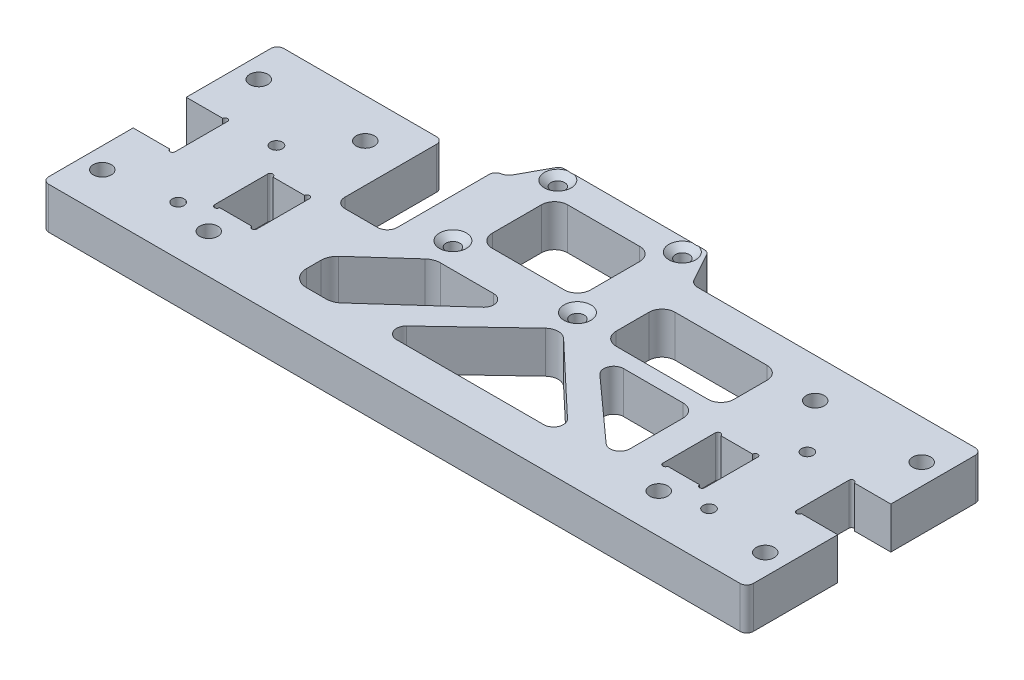
SolidWorks part; units mm, degrees
material "6061 Alloy"
ref_plane "Front Plane" through (0, 0, 0) normal (0, 0, 1) x (1, 0, 0)
ref_plane "Top Plane" through (0, 0, 0) normal (0, 1, 0) x (1, 0, 0)
ref_plane "Right Plane" through (0, 0, 0) normal (1, 0, 0) x (0, 0, -1)
sketch "Sketch1" plane through (0, 0, 0) normal (0, 1, 0) x (1, 0, 0)
  line L0 (107.5, 76.65) -> (107.5, 0) construction
  line L6 (32.7004, 36.1) -> (32.7004, 19.9)
  line L8 (45.6, 36) -> (45.6, 20)
  line L13 (0, 71.75) -> (69.5, 71.75)
  line L14 (69.5, 71.75) -> (75.5, 82.75)
  line L15 (75.5, 82.75) -> (120.5, 82.75)
  line L16 (120.5, 82.75) -> (126.5, 71.75)
  line L17 (126.5, 71.75) -> (215, 71.75)
  line L18 (32.7004, 28) -> (45.6, 28) construction
  line L19 (34.3004, 36.1) -> (44.0063, 36.1)
  line L20 (34.3004, 19.9) -> (44.0063, 19.9)
  line L21 (182.2996, 36.1) -> (182.2996, 19.9)
  line L22 (180.6996, 36.1) -> (170.9937, 36.1)
  line L23 (169.4, 36) -> (169.4, 20)
  line L24 (180.6996, 19.9) -> (170.9937, 19.9)
  line L25 (12.7, 35.875) -> (0, 35.875) construction
  line L29 (12.7, 43.975) -> (12.7, 27.775)
  line L30 (11.1189, 43.975) -> (0, 43.975)
  line L31 (11.1189, 27.775) -> (0, 27.775)
  line L32 (0, 27.775) -> (0, 0)
  line L33 (0, 43.975) -> (0, 71.75)
  line L34 (202.3, 35.875) -> (215, 35.875) construction
  line L35 (215, 43.975) -> (215, 71.75)
  line L36 (215, 27.775) -> (215, 0)
  line L37 (203.8811, 27.775) -> (215, 27.775)
  line L38 (203.8811, 43.975) -> (215, 43.975)
  line L39 (202.3, 43.975) -> (202.3, 27.775)
  line L44 (107.5, 0) -> (215, 0)
  line L46 (107.5, 0) -> (0, 0)
  circle A0 centre (38.85, 59.75) radius 2.75
  circle A5 centre (38.85, 12) radius 2.75
  circle A6 centre (176.15, 59.75) radius 2.75
  circle A7 centre (176.15, 12) radius 2.75
  arc A8 (32.7004, 36.1) -> (34.3004, 36.1) centre (33.5004, 36.1) cw
  arc A9 (45.6, 36) -> (44.0063, 36.1) centre (44.8, 36) ccw
  arc A10 (32.7004, 19.9) -> (34.3004, 19.9) centre (33.5004, 19.9) ccw
  arc A11 (45.6, 20) -> (44.0063, 19.9) centre (44.8, 20) cw
  arc A12 (182.2996, 19.9) -> (180.6996, 19.9) centre (181.4996, 19.9) cw
  arc A13 (182.2996, 36.1) -> (180.6996, 36.1) centre (181.4996, 36.1) ccw
  arc A14 (169.4, 36) -> (170.9937, 36.1) centre (170.2, 36) cw
  arc A15 (169.4, 20) -> (170.9937, 19.9) centre (170.2, 20) ccw
  circle A16 centre (6.35, 12) radius 2.75
  circle A17 centre (6.35, 59.75) radius 2.75
  arc A18 (12.7, 27.775) -> (11.1189, 27.775) centre (11.9095, 27.8976) cw
  arc A19 (12.7, 43.975) -> (11.1189, 43.975) centre (11.9095, 43.8524) ccw
  arc A20 (202.3, 43.975) -> (203.8811, 43.975) centre (203.0905, 43.8524) cw
  arc A21 (202.3, 27.775) -> (203.8811, 27.775) centre (203.0905, 27.8976) ccw
  circle A22 centre (208.65, 59.75) radius 2.75
  circle A23 centre (208.65, 12) radius 2.75
  dimension "D12" = 5.5
  dimension "D16" = 5.5
  dimension "D17" = 0.8
  dimension "D18" = 0.8
  dimension "D19" = 0.8
  dimension "D20" = 0.8
  dimension "D21" = 5.5
  dimension "D22" = 5.5
  dimension "D27" = 0.8
  dimension "D1" = 215
  dimension "D2" = 71.75
  dimension "D5" = 61.9
  dimension "D6" = 12.9
  dimension "D4" = 11
  dimension "D7" = 6
  dimension "D8" = 38
  dimension "D10" = 45
  dimension "D11" = 16.2
  dimension "D14" = 6
  dimension "D13" = 12
  dimension "D25" = 16.2
  dimension "D3" = 12
  dimension "D23" = 16.2
  dimension "D26" = 12.7
extrude "Boss-Extrude1" add sketch "Sketch1" along normal blind 12.7
sketch "Sketch2" plane through (0, 12.7, 0) normal (0, 1, 0) x (1, 0, 0)
  line L1 (50.6, 85.2461) -> (66.6, 85.2461)
  line L2 (50.6, 85.2461) -> (50.6, 38.75)
  line L3 (50.6, 38.75) -> (66.6, 38.75)
  line L4 (66.6, 85.2461) -> (66.6, 38.75)
  line L5 (45.6, 20) -> (45.6, 36) construction
  line L12 (69.5, 71.75) -> (0, 71.75) construction
  dimension "D1" = 5
  dimension "D2" = 16
  dimension "D3" = 33
extrude "Cut-Extrude1" cut sketch "Sketch2" against normal through all
sketch "Sketch3" plane through (0, 12.7, 0) normal (0, 1, 0) x (1, 0, 0)
  line L1 (66.6, 38.75) -> (66.6, 71.75) construction
  line L2 (120.5, 82.75) -> (75.5, 82.75) construction
  circle A0 centre (78.6, 78.75) radius 2.1
  circle A1 centre (78.6, 46.75) radius 2.1
  circle A2 centre (116.6, 78.75) radius 2.1
  circle A3 centre (116.6, 46.75) radius 2.1
  dimension "D2" = 4.2
  dimension "D5" = 4.2
  dimension "D8" = 32
  dimension "D1" = 4
  dimension "D3" = 12
  dimension "D4" = 32
  dimension "D7" = 38
  dimension "D6" = 2
extrude "Cut-Extrude2" cut sketch "Sketch3" against normal through all
sketch "Sketch5" plane through (0, 12.7, 0) normal (0, 1, 0) x (1, 0, 0)
  line L3 (98.7821, 39) -> (82.5187, 39)
  line L11 (78.0261, 13.2835) -> (100.789, 33.7701)
  line L12 (66.6, 38.75) -> (66.6, 71.75) construction
  line L13 (115.8513, 37.7761) -> (94.0759, 17.1795)
  line L14 (118.6, 40.376) -> (118.6, 12) construction
  line L15 (96.1374, 12) -> (141.0626, 12)
  line L16 (121.3487, 37.7761) -> (143.1241, 17.1795)
  line L17 (138.4179, 39) -> (156.6, 39)
  line L18 (155.5931, 16.5062) -> (136.411, 33.7701)
  line L19 (160.6, 35) -> (160.6, 18.7361)
  line L20 (120.5, 82.75) -> (75.5, 82.75) construction
  line L21 (86.6, 73.75) -> (108.6, 73.75)
  line L22 (82.6, 69.75) -> (82.6, 54.75)
  line L23 (86.6, 50.75) -> (108.6, 50.75)
  line L24 (112.6, 69.75) -> (112.6, 54.75)
  line L25 (215, 71.75) -> (126.5, 71.75) construction
  line L26 (131.4, 61.75) -> (159.4, 61.75)
  line L27 (127.4, 57.75) -> (127.4, 47.75)
  line L28 (131.4, 43.75) -> (159.4, 43.75)
  line L29 (163.4, 57.75) -> (163.4, 47.75)
  line L30 (79.1739, 37.7165) -> (65.279, 25.2111)
  line L31 (169.4, 36) -> (169.4, 20) construction
  line L32 (63.6239, 21.4947) -> (63.6239, 17)
  line L33 (68.6239, 12) -> (74.6813, 12)
  arc A0 (121.3487, 37.7761) -> (115.8513, 37.7761) centre (118.6, 34.8701) ccw
  arc A1 (160.6, 35) -> (156.6, 39) centre (156.6, 35) ccw
  arc A3 (112.6, 69.75) -> (108.6, 73.75) centre (108.6, 69.75) ccw
  arc A4 (108.6, 50.75) -> (112.6, 54.75) centre (108.6, 54.75) ccw
  arc A5 (82.6, 54.75) -> (86.6, 50.75) centre (86.6, 54.75) ccw
  arc A6 (82.6, 69.75) -> (86.6, 73.75) centre (86.6, 69.75) cw
  arc A7 (155.5931, 16.5062) -> (160.6, 18.7361) centre (157.6, 18.7361) ccw
  arc A8 (136.411, 33.7701) -> (138.4179, 39) centre (138.4179, 36) cw
  arc A10 (141.0626, 12) -> (143.1241, 17.1795) centre (141.0626, 15) ccw
  arc A11 (96.1374, 12) -> (94.0759, 17.1795) centre (96.1374, 15) cw
  arc A12 (100.789, 33.7701) -> (98.7821, 39) centre (98.7821, 36) ccw
  arc A13 (163.4, 57.75) -> (159.4, 61.75) centre (159.4, 57.75) ccw
  arc A14 (159.4, 43.75) -> (163.4, 47.75) centre (159.4, 47.75) ccw
  arc A15 (127.4, 47.75) -> (131.4, 43.75) centre (131.4, 47.75) ccw
  arc A16 (127.4, 57.75) -> (131.4, 61.75) centre (131.4, 57.75) cw
  arc A17 (79.1739, 37.7165) -> (82.5187, 39) centre (82.5187, 34) cw
  arc A18 (63.6239, 21.4947) -> (65.279, 25.2111) centre (68.6239, 21.4947) cw
  arc A19 (68.6239, 12) -> (63.6239, 17) centre (68.6239, 17) cw
  arc A20 (74.6813, 12) -> (78.0261, 13.2835) centre (74.6813, 17) ccw
  point P25 (160.6, 39)
  point P33 (112.6, 50.75)
  point P36 (82.6, 50.75)
  point P39 (82.6, 73.75)
  point P42 (160.6, 12)
  point P45 (130.6, 39)
  point P48 (76.6, 12)
  point P51 (148.6, 12)
  point P54 (88.6, 12)
  point P57 (106.6, 39)
  point P68 (163.4, 61.75)
  point P71 (163.4, 43.75)
  point P76 (127.4, 61.75)
  dimension "D11" = 4
  dimension "D12" = 3
  dimension "D13" = 3
  dimension "D14" = 3
  dimension "D19" = 4
  dimension "D2" = 5
  dimension "D4" = 5
  dimension "D3" = 12
  dimension "D6" = 30
  dimension "D7" = 9
  dimension "D8" = 16
  dimension "D9" = 23
  dimension "D10" = 30
  dimension "D15" = 10
  dimension "D16" = 18
  dimension "D17" = 6
  dimension "D18" = 36
extrude "Cut-Extrude3" cut sketch "Sketch5" against normal through all
fillet "Fillet1" radius 3 4 edges at (69.5, 6.35, -71.75) (66.6, 6.35, -38.75) (50.6, 6.35, -38.75) (126.5, 6.35, -71.75)
fillet "Fillet2" radius 2 8 edges at (215, 6.35, -71.75) (120.5, 6.35, -82.75) (75.5, 6.35, -82.75) (50.6, 6.35, -71.75) (66.6, 6.35, -71.75) (0, 6.35, -71.75) (215, 6.35, 0) (0, 6.35, 0)
sketch "Sketch6" plane through (0, 12.7, 0) normal (0, 1, 0) x (1, 0, 0)
  line L0 (2, 0) -> (213, 0) construction
  line L1 (107.5, 92.584) -> (107.5, -38.973) construction
  line L2 (215, 2) -> (215, 27.775) construction
  circle A0 centre (188.5, 45) radius 1.8
  circle A1 centre (176.15, 59.75) radius 2.75 construction
  circle A2 centre (188.5, 15) radius 1.8
  circle A3 centre (26.5, 45) radius 1.8
  circle A4 centre (26.5, 15) radius 1.8
  dimension "D2" = 3.6
  dimension "D5" = 3.6
  dimension "D1" = 12.35
  dimension "D3" = 45
  dimension "D4" = 15
  dimension "D6" = 107.5
extrude "Cut-Extrude4" cut sketch "Sketch6" against normal through all
chamfer "Chamfer1" distance 2 angle 40 4 edges at (116.6, 12.7, -76.65) (116.6, 12.7, -44.65) (78.6, 12.7, -44.65) (78.6, 12.7, -76.65) first distance on face at (188.5, 12.7, -13.2)
equation "\"DriveMotorLength\"= 90mm"
equation "\"DriveMotorGap\"= 10mm"
equation "\"AluminumThickness\"= 0.5in"
equation "\"ChassisWidth\"= ( \"DriveMotorLength\" + \"AluminumThickness\" ) * 2 + \"DriveMotorGap\""
equation "\"RepeatMagnumHoleWidth\"= 19.05mm"
equation "\"MortiseWidth\"= 16mm"
equation "\"ChassisScrewThruHole\"= 5.5mm"
equation "\"D11@Sketch1\"=\"MortiseSlotWidth\""
equation "\"D12@Sketch1\"=\"ChassisScrewThruHole\""
equation "\"D16@Sketch1\"=\"ChassisScrewThruHole\""
equation "\"MortiseSlotWidth\"= 16.2mm"
equation "\"Dogbone\"= 0.8mm"
equation "\"D17@Sketch1\"=\"Dogbone\""
equation "\"D18@Sketch1\"=\"Dogbone\""
equation "\"D19@Sketch1\"=\"Dogbone\""
equation "\"D20@Sketch1\"=\"Dogbone\""
equation "\"D21@Sketch1\"=\"ChassisScrewThruHole\""
equation "\"D22@Sketch1\"=\"ChassisScrewThruHole\""
equation "\"D27@Sketch1\"=\"Dogbone\""
equation "\"D23@Sketch1\"=\"MortiseSlotWidth\""
equation "\"D25@Sketch1\"=\"MortiseSlotWidth\""
